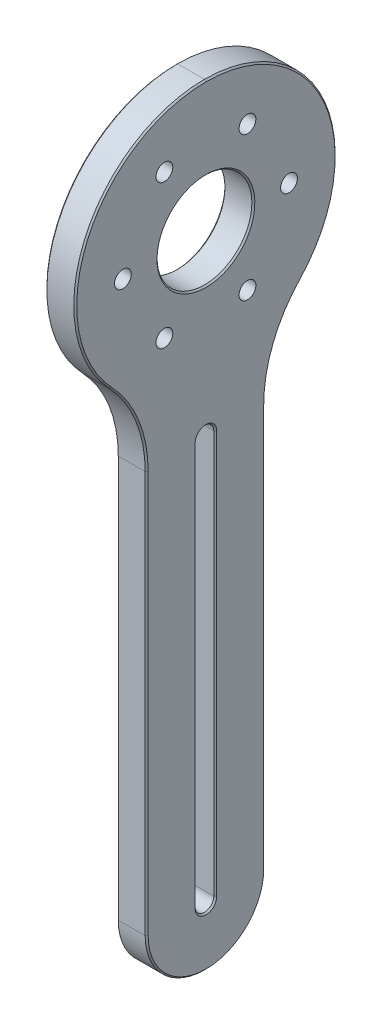
SolidWorks part; units mm, degrees
note: '?' marks a value the reader was unsure of.
material "Plain Carbon Steel"
ref_plane "Front Plane" through (0, 0, 0) normal (0, 0, 1) x (1, 0, 0)
ref_plane "Top Plane" through (0, 0, 0) normal (0, 1, 0) x (1, 0, 0)
ref_plane "Right Plane" through (0, 0, 0) normal (1, 0, 0) x (0, 0, -1)
sketch "Sketch1" plane through (0, 0, 0) normal (0, 0, 1) x (1, 0, 0)
  line L0 (0, 105) -> (0, 0)
  line L4 (8, 0) -> (8, 105)
  line L5 (8, 105) -> (0, 105)
  line L6 (0, 0) -> (8, 0)
  dimension "D1" = 8
  dimension "D2" = 105
extrude "base" add sketch "Sketch1" along normal mid plane 70
hole_wizard "CSK for M4 Countersunk Flat Head Screw2" positions "Sketch5" profile "Sketch6" countersink size "M4" standard "ISO" end condition up to next
sketch "Sketch5" plane through (0, 0, 0) normal (-1, 0, 0) x (0, 0, 1)
  circle A0 centre (0, 70) radius 22.25 construction
  point P6 (-22.25, 70)
  point P14 (-11.125, 89.2691)
  point P15 (11.125, 89.2691)
  point P16 (22.25, 70)
  point P17 (11.125, 50.7309)
  point P18 (-11.125, 50.7309)
  dimension "D1" = 44.5
  dimension "D2" = 70
  dimension "D3" = 6
sketch "Sketch6" plane through (0, 50.7309, -11.125) normal (0, 1, 0) x (0, 0, 1)
  line L0 (0, 0) -> (0, 8)
  line L1 (0, 8) -> (2.25, 8)
  line L2 (2.25, 8) -> (2.25, 2.45)
  line L3 (2.25, 2.45) -> (4.7, 0)
  line L5 (4.7, 0) -> (0, 0)
  line L6 (-2.25, 2.45) -> (-4.7, 0) construction
  line L11 (0, -6.35) -> (0, 107.95) construction
  dimension "Thru Hole Dia." = 4.5
  dimension "Thru Hole Depth" = 8
  dimension "Near C'Sink Dia." = 9.4
  dimension "Near C'Sink Angle" = 90
fillet "Fillet1" radius 35 2 edges at (4, 105, 35) (4, 105, -35)
sketch "Sketch7" plane through (0, 0, 0) normal (-1, 0, 0) x (0, 0, 1)
  line L0 (0, 0) -> (0, 70) construction
  dimension "D1" = 70
sketch "Sketch8" plane through (0, 0, 0) normal (0, -1, 0) x (1, 0, 0)
  line L1 (0, -35) -> (8, -35)
  line L2 (0, -35) -> (0, 35)
  line L3 (0, 35) -> (8, 35)
  line L4 (8, -35) -> (8, 35)
extrude "Boss-Extrude1" add sketch "Sketch8" along normal blind 101.6
sketch "Sketch9" plane through (0, 0, 0) normal (-1, 0, 0) x (0, 0, 1)
  line L0 (0, 105) -> (0, -101.6) construction
  line L1 (35, -101.6) -> (-35, -101.6) construction
  line L2 (0, 22.225) -> (0, -85.725) construction
  line L3 (2.5, 22.225) -> (2.5, -85.725)
  line L4 (-2.5, 22.225) -> (-2.5, -85.725)
  arc A0 (2.5, 22.225) -> (-2.5, 22.225) centre (0, 22.225) ccw
  arc A1 (-2.5, -85.725) -> (2.5, -85.725) centre (0, -85.725) ccw
  point P7 (0, -31.75)
  dimension "D1" = 15.875
  dimension "D2" = 107.95
  dimension "D3" = 5
extrude "Cut-Extrude1" cut sketch "Sketch9" against normal up to next
sketch "Sketch10" plane through (8, 0, 0) normal (1, 0, 0) x (0, 0, -1)
  line L0 (0, -101.6) -> (0, 105) construction
  line L1 (35, -101.6) -> (-35, -101.6) construction
  line L2 (15.875, -101.6) -> (15.875, 38.8073)
  line L3 (-15.875, -101.6) -> (-15.875, 38.8073)
  line L4 (-15.875, -101.6) -> (-15.875, 105) construction
  line L5 (15.875, -101.6) -> (15.875, 105) construction
  line L6 (-35, 70) -> (-35, -101.6)
  line L7 (-35, -101.6) -> (-15.875, -101.6)
  line L8 (15.875, -101.6) -> (35, -101.6)
  line L9 (35, -101.6) -> (35, 70)
  arc A0 (0, 105) -> (-35, 70) centre (0, 70) ccw construction
  arc A1 (15.875, 38.8073) -> (-15.875, 38.8073) centre (0, 70) ccw
  line M14 (-35, 70) -> (-35, -101.6)
  line M15 (-35, -101.6) -> (35, -101.6)
  line M16 (35, -101.6) -> (35, 70)
  dimension "D1" = 15.875
  dimension "D2" = 15.875
extrude "Cut-Extrude2" cut sketch "Sketch10" against normal through all contours A1 L2 M15 M16 | A1 L3 M14 M15
fillet "Fillet2" radius 34.925 2 edges at (4, 38.8073, -15.875) (4, 38.8073, 15.875)
fillet "Fillet3" radius 15.875 2 edges at (4, -101.6, -15.875) (4, -101.6, 15.875)
sketch "Sketch12" plane through (0, 0, 0) normal (-1, 0, 0) x (0, 0, 1)
  circle A0 centre (0, 70) radius 12.7
  dimension "D1" = 25.4
extrude "Cut-Extrude4" cut sketch "Sketch12" against normal through all
ref_axis "Axis1" through (8, 70, 0) along (-1, 0, 0)?
chamfer "Chamfer1" distance 0.3969 angle 45 26 edges at (8, 83.8422, -32.1464) (0, 83.8422, 32.1464) (8, 34.8647, -18.3508) (0, 34.8647, -18.3508) (8, 34.8647, 18.3508) (0, 34.8647, 18.3508) (8, -31.8878, -15.875) (8, -31.8878, 15.875) (8, -96.9503, 11.2253) (8, -96.9503, -11.2253) (0, -31.8878, -15.875) (0, -31.8878, 15.875) (0, -96.9503, 11.2253) (0, -96.9503, -11.2253) (8, 57.3, 0) (0, 57.3, 0) (0, 83.8422, -32.1464) (8, 83.8422, 32.1464) (0, 24.725, 0) (0, -31.75, -2.5) (0, -88.225, 0) (0, -31.75, 2.5) (8, -31.75, -2.5) (8, 24.725, 0) (8, -31.75, 2.5) (8, -88.225, 0)
